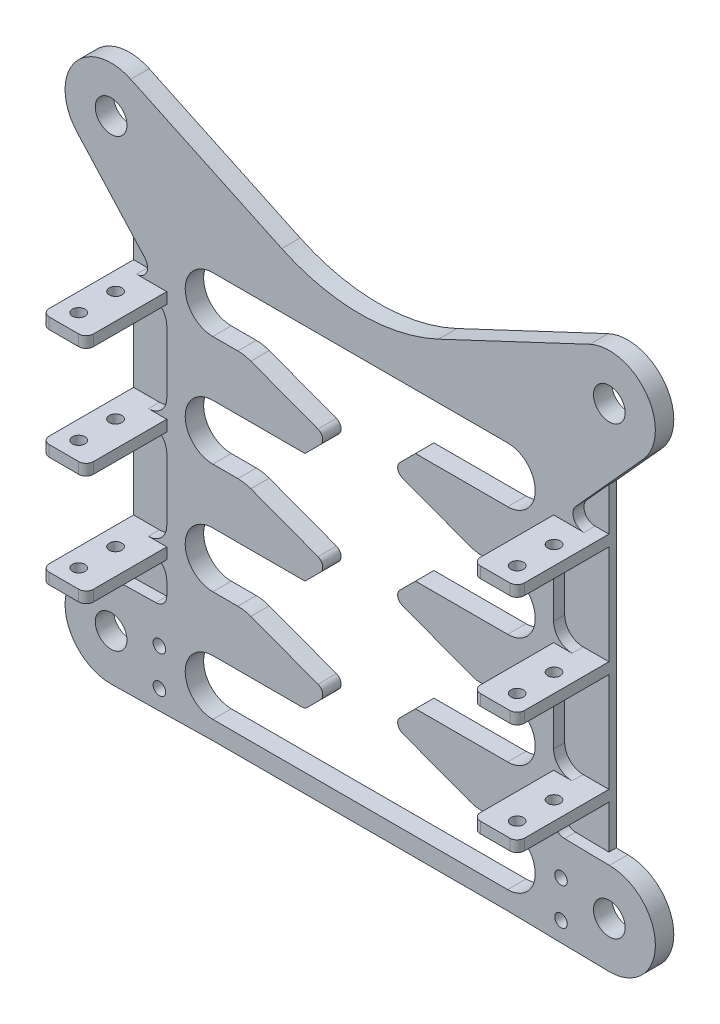
SolidWorks part; units mm, degrees
ref_plane "Front Plane" through (0, 0, 0) normal (0, 0, 1) x (1, 0, 0)
ref_plane "Top Plane" through (0, 0, 0) normal (0, 1, 0) x (1, 0, 0)
ref_plane "Right Plane" through (0, 0, 0) normal (1, 0, 0) x (0, 0, -1)
ref_plane "Plane1" through (0, 0, 60) normal (0, 0, 1) x (1, 0, 0)
sketch "Sketch2" plane through (0, 0, 60) normal (0, 0, 1) x (1, 0, 0)
  line L0 (0, 52) -> (-40, 52)
  line L1 (0, 52) -> (40, 52)
  line L2 (0, 52) -> (0, 82)
  line L3 (0, 52) -> (0, 22)
  line L4 (0, 82) -> (40, 82)
  line L5 (0, 82) -> (-40, 82)
  line L6 (0, 22) -> (40, 22)
  line L7 (0, 22) -> (-40, 22)
  line L8 (0, 22) -> (0, -8)
  line L9 (0, -8) -> (40, -8)
  line L10 (0, -8) -> (-40, -8)
  line L11 (40, 82) -> (-40, 82) construction
  line L12 (40, 74.5) -> (-40, 74.5)
  line L13 (40, 89.5) -> (-40, 89.5)
  line L14 (-40, 52) -> (40, 52) construction
  line L15 (-40, 59.5) -> (40, 59.5)
  line L16 (-40, 44.5) -> (40, 44.5)
  line L17 (40, 22) -> (-40, 22) construction
  line L18 (40, 14.5) -> (-40, 14.5)
  line L19 (40, 29.5) -> (-40, 29.5)
  line L20 (40, -8) -> (-40, -8) construction
  line L21 (40, -15.5) -> (-40, -15.5)
  line L22 (40, -0.5) -> (-40, -0.5)
  line L23 (0, -8) -> (0, 82) construction
  line L24 (-7.5, -8) -> (-7.5, 82)
  line L25 (7.5, -8) -> (7.5, 82)
  line L26 (40, 69.5) -> (-40, 69.5)
  line L27 (40, 94.5) -> (-40, 94.5)
  line L28 (-40, 64.5) -> (40, 64.5)
  line L29 (-40, 39.5) -> (40, 39.5)
  line L30 (-12.5, -8) -> (-12.5, 82)
  line L31 (12.5, -8) -> (12.5, 82)
  line L32 (40, 9.5) -> (-40, 9.5)
  line L33 (40, 34.5) -> (-40, 34.5)
  line L34 (40, -20.5) -> (-40, -20.5)
  line L35 (40, 4.5) -> (-40, 4.5)
  arc A0 (40, 74.5) -> (40, 89.5) centre (40, 82) ccw
  arc A1 (-40, 89.5) -> (-40, 74.5) centre (-40, 82) ccw
  arc A2 (-40, 59.5) -> (-40, 44.5) centre (-40, 52) ccw
  arc A3 (40, 44.5) -> (40, 59.5) centre (40, 52) ccw
  arc A4 (40, 14.5) -> (40, 29.5) centre (40, 22) ccw
  arc A5 (-40, 29.5) -> (-40, 14.5) centre (-40, 22) ccw
  arc A6 (40, -15.5) -> (40, -0.5) centre (40, -8) ccw
  arc A7 (-40, -0.5) -> (-40, -15.5) centre (-40, -8) ccw
  arc A8 (-7.5, -8) -> (7.5, -8) centre (0, -8) ccw
  arc A9 (7.5, 82) -> (-7.5, 82) centre (0, 82) ccw
  arc A10 (-40, 94.5) -> (-40, 69.5) centre (-40, 82) ccw
  arc A11 (40, 69.5) -> (40, 94.5) centre (40, 82) ccw
  arc A12 (40, 39.5) -> (40, 64.5) centre (40, 52) ccw
  arc A13 (-40, 64.5) -> (-40, 39.5) centre (-40, 52) ccw
  arc A14 (12.5, 82) -> (-12.5, 82) centre (0, 82) ccw
  arc A15 (-12.5, -8) -> (12.5, -8) centre (0, -8) ccw
  arc A16 (-40, 34.5) -> (-40, 9.5) centre (-40, 22) ccw
  arc A17 (40, 9.5) -> (40, 34.5) centre (40, 22) ccw
  arc A18 (-40, 4.5) -> (-40, -20.5) centre (-40, -8) ccw
  arc A19 (40, -20.5) -> (40, 4.5) centre (40, -8) ccw
  point P3 (0, 82)
  point P19 (0, 52)
  point P24 (0, 22)
  point P29 (0, -8)
  point P34 (0, 37)
  dimension "D1" = 40
  dimension "D2" = 40
  dimension "D3" = 30
  dimension "D4" = 30
  dimension "D5" = 30
  dimension "D6" = 40
  dimension "D7" = 40
  dimension "D8" = 40
  dimension "D9" = 40
  dimension "D10" = 40
  dimension "D11" = 40
  dimension "D12" = 15
  dimension "D13" = 15
  dimension "D14" = 15
  dimension "D15" = 15
  dimension "D16" = 15
  dimension "D17" = 5
extrude "Boss-Extrude2" add sketch "Sketch2" along normal blind 5 contours A14 L13 A0 L12 L31 L26 A11 L27 | L29 A12 L28 L31 L15 A3 L16 | L32 A17 L33 L31 L19 A4 L18 | L34 A19 L35 L31 L22 A6 L21 A15 | L31 L35 L25 L22 | L35 L31 L32 L25 | L32 L31 L18 L25 | L31 L33 L25 L19 | L33 L31 L29 L25 | L29 L31 L16 L25 | L15 L31 L28 L25 | L28 L31 L26 L25 | L26 L31 L12 L25 | L13 A14 | L21 A15 | L35 A18 L34 A15 L21 A7 L22 L30 | L24 L35 L30 L22 | L35 L24 L32 L30 | L32 L24 L18 L30 | L33 A16 L32 L30 L18 A5 L19 | L24 L33 L30 L19 | L33 L24 L29 L30 | L30 L29 L24 L16 | L28 A13 L29 L30 L16 A2 L15 | L30 L15 L24 L28 | L30 L28 L24 L26 | L30 L26 L24 L12 | A14 L27 A10 L26 L30 L12 A1 L13 region at (-10, 42, 60) region at (-10, 62, 60) region at (10, 42, 60) region at (10, 62, 60) region at (-12.9717, 42, 60) region at (-10, 37, 60) region at (-10, 67, 60) region at (26.25, 44.0283, 60) region at (10, 37, 60) region at (10, 67, 60) region at (-10, 32, 60) region at (-10, 72, 60) region at (10, 32, 60) region at (10, 72, 60) region at (-12.9717, 32, 60) region at (-26.25, 70.0815, 60) region at (26.25, 34.0283, 60) region at (13.0815, 72, 60) region at (-10, 12, 60) region at (0, 91.5388, 60) region at (10, 12, 60) region at (-10, 7, 60) region at (10, 7, 60) region at (-10, 2, 60) region at (-13.0815, 2, 60) region at (26.25, 3.9185, 60) region at (10, 2, 60) region at (0, -17.5388, 60)
chamfer "Chamfer1" distance 7.5 angle 45 12 edges at (7.5, 44.5, 62.5) (-7.5, 44.5, 62.5) (-7.5, 14.5, 62.5) (7.5, 14.5, 62.5) (-7.5, 29.5, 62.5) (-7.5, -0.5, 62.5) (7.5, -0.5, 62.5) (7.5, 29.5, 62.5) (-7.5, 74.5, 62.5) (-7.5, 59.5, 62.5) (7.5, 74.5, 62.5) (7.5, 59.5, 62.5)
chamfer "Chamfer2" distance 5 angle 45 12 edges at (12.5, 64.5, 62.5) (12.5, 69.5, 62.5) (12.5, 34.5, 62.5) (12.5, 39.5, 62.5) (-12.5, 64.5, 62.5) (-12.5, 69.5, 62.5) (-12.5, 39.5, 62.5) (-12.5, 34.5, 62.5) (-12.5, 4.5, 62.5) (-12.5, 9.5, 62.5) (12.5, 9.5, 62.5) (12.5, 4.5, 62.5)
fillet "Fillet2" radius 1.5 18 edges at (17.5, 64.5, 62.5) (17.5, 69.5, 62.5) (17.5, 39.5, 62.5) (17.5, 34.5, 62.5) (17.5, 9.5, 62.5) (17.5, 4.5, 62.5) (-17.5, 69.5, 62.5) (-17.5, 64.5, 62.5) (-17.5, 39.5, 62.5) (-17.5, 34.5, 62.5) (-17.5, 4.5, 62.5) (-17.5, 9.5, 62.5) (-15, 67, 62.5) (15, 67, 62.5) (-15, 37, 62.5) (15, 37, 62.5) (-15, 7, 62.5) (15, 7, 62.5)
sketch "Sketch3" plane through (0, 0, 60) normal (0, 0, -1) x (-1, 0, 0)
  line L0 (-67.6066, -21.0066) -> (-40, -20.5)
  line L1 (67.6066, -21.0066) -> (40, -20.5)
  line L2 (67.6066, 3.9934) -> (40, 4.5)
  line L3 (-67.6066, 3.9934) -> (-40, 4.5)
  line L4 (-62.2831, 123.8164) -> (0, 94.5)
  line L5 (-76.875, 104.1193) -> (-49.2684, 73.6127)
  line L6 (-40, 94.5) -> (40, 94.5) construction
  line L7 (0, 94.5) -> (62.2831, 123.8164)
  line L8 (76.875, 104.1193) -> (49.2684, 73.6127)
  line L9 (-40, 94.5) -> (40, 94.5)
  circle A0 centre (67.6066, 112.5066) radius 4.3
  circle A1 centre (-67.6066, 112.5066) radius 4.3
  circle A2 centre (-67.6066, -8.5066) radius 4.3
  circle A3 centre (67.6066, -8.5066) radius 4.3
  circle A4 centre (67.6066, -8.5066) radius 12.5
  circle A5 centre (67.6066, 112.5066) radius 12.5
  circle A6 centre (-67.6066, 112.5066) radius 12.5
  circle A7 centre (-67.6066, -8.5066) radius 12.5
  arc A8 (-40, 94.5) -> (-40, 69.5) centre (-40, 82) ccw construction
  arc A9 (-40, 94.5) -> (-49.2684, 73.6127) centre (-40, 82) ccw
  arc A10 (40, 69.5) -> (40, 94.5) centre (40, 82) ccw construction
  arc A11 (49.2684, 73.6127) -> (40, 94.5) centre (40, 82) ccw
  arc A12 (40, -20.5) -> (40, 4.5) centre (40, -8) ccw construction
  arc A13 (-40, 4.5) -> (-40, -20.5) centre (-40, -8) ccw construction
  arc A14 (40, -20.5) -> (40, 4.5) centre (40, -8) ccw
  arc A15 (-40, 4.5) -> (-40, -20.5) centre (-40, -8) ccw
extrude "Boss-Extrude3" add sketch "Sketch3" against normal blind 5 contours A9 L9 L4 A6 L5 | A6 A1 | A11 L8 A5 L7 L9 | A5 A0 | A4 L1 A3 | A14 L1 A4 L2 | A7 L0 A2 | A15 L3 A7 L0 region at (79.753, -8.5066, 60) region at (53.8033, -8.2533, 60) region at (-67.3838, -20.6489, 60) region at (-53.8033, -8.2533, 60) region at (-43.2431, 100.4549, 60) region at (43.2431, 100.4549, 60) region at (57.3507, 119.0144, 60) region at (-74.1144, 122.7625, 60)
fillet "Fillet3" radius 50 1 edges at (0, 94.5, 62.5)
sketch "Sketch4" plane through (0, 0, 65) normal (0, 0, 1) x (1, 0, 0)
  line L0 (-17.0607, 9.0607) -> (-16.0607, 8.0607) construction
  line L1 (-16.0607, 5.9393) -> (-17.0607, 4.9393) construction
  line L2 (-67.6066, 3.9934) -> (-40.4586, 4.4916) construction
  line L3 (-18.1213, 4.5) -> (-40, 4.5) construction
  line L4 (-18.1213, 9.5) -> (-40, 9.5) construction
  line L5 (-18.1213, 34.5) -> (-40, 34.5) construction
  line L6 (-16.0607, 35.9393) -> (-17.0607, 34.9393) construction
  line L7 (-17.0607, 39.0607) -> (-16.0607, 38.0607) construction
  line L8 (-40, 39.5) -> (-18.1213, 39.5) construction
  line L9 (-40, 64.5) -> (-18.1213, 64.5) construction
  line L10 (-16.0607, 65.9393) -> (-17.0607, 64.9393) construction
  line L11 (-17.0607, 69.0607) -> (-16.0607, 68.0607) construction
  line L12 (-18.1213, 69.5) -> (-40, 69.5) construction
  line L13 (-17.0607, 9.0607) -> (-16.0607, 8.0607)
  line L14 (-16.0607, 5.9393) -> (-17.0607, 4.9393)
  line L15 (-67.6066, 3.9934) -> (-40.4586, 4.4916)
  line L16 (-18.1213, 4.5) -> (-40, 4.5)
  line L17 (-18.1213, 9.5) -> (-40, 9.5)
  line L18 (-18.1213, 34.5) -> (-40, 34.5)
  line L19 (-16.0607, 35.9393) -> (-17.0607, 34.9393)
  line L20 (-17.0607, 39.0607) -> (-16.0607, 38.0607)
  line L21 (-40, 39.5) -> (-18.1213, 39.5)
  line L22 (-40, 64.5) -> (-18.1213, 64.5)
  line L23 (-16.0607, 65.9393) -> (-17.0607, 64.9393)
  line L24 (-17.0607, 69.0607) -> (-16.0607, 68.0607)
  line L25 (-18.1213, 69.5) -> (-40, 69.5)
  line L26 (-52.5, 22) -> (-52.5, 82)
  line L27 (-52.5, 82) -> (-52.5, 0)
  line L28 (-76.875, 104.1193) -> (-49.2684, 73.6127) construction
  line L29 (-76.875, 104.1193) -> (-49.2684, 73.6127)
  arc A0 (-17.0607, 9.0607) -> (-18.1213, 9.5) centre (-18.1213, 8) ccw construction
  arc A1 (-16.0607, 5.9393) -> (-16.0607, 8.0607) centre (-17.1213, 7) ccw construction
  arc A2 (-18.1213, 4.5) -> (-17.0607, 4.9393) centre (-18.1213, 6) ccw construction
  arc A3 (-40, 34.5) -> (-40, 9.5) centre (-40, 22) ccw construction
  arc A4 (-18.1213, 34.5) -> (-17.0607, 34.9393) centre (-18.1213, 36) ccw construction
  arc A5 (-16.0607, 35.9393) -> (-16.0607, 38.0607) centre (-17.1213, 37) ccw construction
  arc A6 (-17.0607, 39.0607) -> (-18.1213, 39.5) centre (-18.1213, 38) ccw construction
  arc A7 (-49.2684, 73.6127) -> (-40, 69.5) centre (-40, 82) ccw construction
  arc A8 (-40, 64.5) -> (-40, 39.5) centre (-40, 52) ccw construction
  arc A9 (-18.1213, 64.5) -> (-17.0607, 64.9393) centre (-18.1213, 66) ccw construction
  arc A10 (-16.0607, 65.9393) -> (-16.0607, 68.0607) centre (-17.1213, 67) ccw construction
  arc A11 (-17.0607, 69.0607) -> (-18.1213, 69.5) centre (-18.1213, 68) ccw construction
  arc A12 (-17.0607, 9.0607) -> (-18.1213, 9.5) centre (-18.1213, 8) ccw
  arc A13 (-16.0607, 5.9393) -> (-16.0607, 8.0607) centre (-17.1213, 7) ccw
  arc A14 (-18.1213, 4.5) -> (-17.0607, 4.9393) centre (-18.1213, 6) ccw
  arc A15 (-40, 34.5) -> (-40, 9.5) centre (-40, 22) ccw
  arc A16 (-18.1213, 34.5) -> (-17.0607, 34.9393) centre (-18.1213, 36) ccw
  arc A17 (-16.0607, 35.9393) -> (-16.0607, 38.0607) centre (-17.1213, 37) ccw
  arc A18 (-17.0607, 39.0607) -> (-18.1213, 39.5) centre (-18.1213, 38) ccw
  arc A19 (-49.2684, 73.6127) -> (-40, 69.5) centre (-40, 82) ccw
  arc A20 (-40, 64.5) -> (-40, 39.5) centre (-40, 52) ccw
  arc A21 (-18.1213, 64.5) -> (-17.0607, 64.9393) centre (-18.1213, 66) ccw
  arc A22 (-16.0607, 65.9393) -> (-16.0607, 68.0607) centre (-17.1213, 67) ccw
  arc A23 (-17.0607, 69.0607) -> (-18.1213, 69.5) centre (-18.1213, 68) ccw
  arc A24 (-40, 4.5) -> (-40.4586, 4.4916) centre (-40, -8) ccw construction
  arc A25 (-40, 4.5) -> (-40.4586, 4.4916) centre (-40, -8) ccw
extrude "Boss-Extrude4" add sketch "Sketch4" against normal up to surface (5 mm away) contours A25 L16 A14 L14 A13 L13 A12 L17 A15 L27 L15 | A20 L26 A15 L18 A16 L19 A17 L20 A18 L21 | L24 A23 L25 A19 L29 L27 A20 L22 A21 L23 A22 region at (-38.4155, 66.8833, 65) region at (-38.5639, 37, 65) region at (-36.8959, 7.8058, 65) up to face at (0, 39.4897, 60)
sketch "Sketch5" plane through (0, 0, 65) normal (0, 0, 1) x (1, 0, 0)
  line L0 (67.6066, 3.9934) -> (40.4586, 4.4916) construction
  line L1 (40, 4.5) -> (18.1213, 4.5) construction
  line L2 (17.0607, 4.9393) -> (16.0607, 5.9393) construction
  line L3 (16.0607, 8.0607) -> (17.0607, 9.0607) construction
  line L4 (40, 9.5) -> (18.1213, 9.5) construction
  line L5 (40, 34.5) -> (18.1213, 34.5) construction
  line L6 (17.0607, 34.9393) -> (16.0607, 35.9393) construction
  line L7 (16.0607, 38.0607) -> (17.0607, 39.0607) construction
  line L8 (18.1213, 39.5) -> (40, 39.5) construction
  line L9 (18.1213, 64.5) -> (40, 64.5) construction
  line L10 (17.0607, 64.9393) -> (16.0607, 65.9393) construction
  line L11 (16.0607, 68.0607) -> (17.0607, 69.0607) construction
  line L12 (40, 69.5) -> (18.1213, 69.5) construction
  line L13 (76.875, 104.1193) -> (49.2684, 73.6127) construction
  line L14 (67.6066, 3.9934) -> (40.4586, 4.4916)
  line L15 (40, 4.5) -> (18.1213, 4.5)
  line L16 (17.0607, 4.9393) -> (16.0607, 5.9393)
  line L17 (16.0607, 8.0607) -> (17.0607, 9.0607)
  line L18 (40, 9.5) -> (18.1213, 9.5)
  line L19 (40, 34.5) -> (18.1213, 34.5)
  line L20 (17.0607, 34.9393) -> (16.0607, 35.9393)
  line L21 (16.0607, 38.0607) -> (17.0607, 39.0607)
  line L22 (18.1213, 39.5) -> (40, 39.5)
  line L23 (18.1213, 64.5) -> (40, 64.5)
  line L24 (17.0607, 64.9393) -> (16.0607, 65.9393)
  line L25 (16.0607, 68.0607) -> (17.0607, 69.0607)
  line L26 (40, 69.5) -> (18.1213, 69.5)
  line L27 (52.5, 77.1838) -> (49.2684, 73.6127)
  line L28 (52.5, 22) -> (52.5, 4.2706)
  line L29 (52.5, 4.2706) -> (52.5, 77.1838)
  arc A0 (40.4586, 4.4916) -> (40, 4.5) centre (40, -8) ccw construction
  arc A1 (17.0607, 4.9393) -> (18.1213, 4.5) centre (18.1213, 6) ccw construction
  arc A2 (16.0607, 8.0607) -> (16.0607, 5.9393) centre (17.1213, 7) ccw construction
  arc A3 (18.1213, 9.5) -> (17.0607, 9.0607) centre (18.1213, 8) ccw construction
  arc A4 (40, 9.5) -> (40, 34.5) centre (40, 22) ccw construction
  arc A5 (17.0607, 34.9393) -> (18.1213, 34.5) centre (18.1213, 36) ccw construction
  arc A6 (16.0607, 38.0607) -> (16.0607, 35.9393) centre (17.1213, 37) ccw construction
  arc A7 (18.1213, 39.5) -> (17.0607, 39.0607) centre (18.1213, 38) ccw construction
  arc A8 (40, 39.5) -> (40, 64.5) centre (40, 52) ccw construction
  arc A9 (17.0607, 64.9393) -> (18.1213, 64.5) centre (18.1213, 66) ccw construction
  arc A10 (16.0607, 68.0607) -> (16.0607, 65.9393) centre (17.1213, 67) ccw construction
  arc A11 (18.1213, 69.5) -> (17.0607, 69.0607) centre (18.1213, 68) ccw construction
  arc A12 (40, 69.5) -> (49.2684, 73.6127) centre (40, 82) ccw construction
  arc A13 (40.4586, 4.4916) -> (40, 4.5) centre (40, -8) ccw
  arc A14 (17.0607, 4.9393) -> (18.1213, 4.5) centre (18.1213, 6) ccw
  arc A15 (16.0607, 8.0607) -> (16.0607, 5.9393) centre (17.1213, 7) ccw
  arc A16 (18.1213, 9.5) -> (17.0607, 9.0607) centre (18.1213, 8) ccw
  arc A17 (40, 9.5) -> (40, 34.5) centre (40, 22) ccw
  arc A18 (17.0607, 34.9393) -> (18.1213, 34.5) centre (18.1213, 36) ccw
  arc A19 (16.0607, 38.0607) -> (16.0607, 35.9393) centre (17.1213, 37) ccw
  arc A20 (18.1213, 39.5) -> (17.0607, 39.0607) centre (18.1213, 38) ccw
  arc A21 (40, 39.5) -> (40, 64.5) centre (40, 52) ccw
  arc A22 (17.0607, 64.9393) -> (18.1213, 64.5) centre (18.1213, 66) ccw
  arc A23 (16.0607, 68.0607) -> (16.0607, 65.9393) centre (17.1213, 67) ccw
  arc A24 (18.1213, 69.5) -> (17.0607, 69.0607) centre (18.1213, 68) ccw
  arc A25 (40, 69.5) -> (49.2684, 73.6127) centre (40, 82) ccw
extrude "Boss-Extrude5" add sketch "Sketch5" against normal up to surface (5 mm away) contours A25 L26 A24 L25 A23 L24 A22 L23 A21 L29 L27 | A21 L22 A20 L21 A19 L20 A18 L19 A17 L29 | A17 L18 A16 L17 A15 L16 A14 L15 A13 L14 L28 region at (38.4155, 66.8833, 65) region at (38.5639, 37, 65) region at (36.8959, 7.8058, 65) up to face at (13.901, 41.0917, 60)
sketch "Sketch7" plane through (0, 0, 65) normal (0, 0, 1) x (1, 0, 0)
  line L0 (-47.5, 52) -> (-48.5, 52)
  line L1 (-47.5, 22) -> (-48.5, 22)
  line L2 (-47.5, -8) -> (-48.5, -8)
  line L3 (47.5, -8) -> (48.5, -8)
  line L4 (47.5, 22) -> (48.5, 22)
  line L5 (47.5, 52) -> (48.5, 52)
  line L6 (47.5, 82) -> (48.5, 82)
  line L7 (-47.5, 82) -> (-48.5, 82)
  line L8 (-47.5, 53) -> (-48.5, 53)
  line L9 (-47.5, 23) -> (-48.5, 23)
  line L10 (-47.5, -7) -> (-48.5, -7)
  line L11 (47.5, -9) -> (48.5, -9)
  line L12 (47.5, 21) -> (48.5, 21)
  line L13 (47.5, 51) -> (48.5, 51)
  line L14 (47.5, 81) -> (48.5, 81)
  line L15 (-47.5, 83) -> (-48.5, 83)
  line L16 (-47.5, 51) -> (-48.5, 51)
  line L17 (-47.5, 21) -> (-48.5, 21)
  line L18 (-47.5, -9) -> (-48.5, -9)
  line L19 (47.5, -7) -> (48.5, -7)
  line L20 (47.5, 23) -> (48.5, 23)
  line L21 (47.5, 53) -> (48.5, 53)
  line L22 (47.5, 83) -> (48.5, 83)
  line L23 (-47.5, 81) -> (-48.5, 81)
  line L24 (-47.5, 53) -> (-47.5, 51)
  line L25 (-48.5, 51) -> (-48.5, 53)
  line L26 (-48.5, 83) -> (-48.5, 81)
  line L27 (-47.5, 81) -> (-47.5, 83)
  line L28 (48.5, 83) -> (48.5, 81)
  line L29 (47.5, 81) -> (47.5, 83)
  line L30 (47.5, 53) -> (47.5, 51)
  line L31 (48.5, 51) -> (48.5, 53)
  line L32 (47.5, 23) -> (47.5, 21)
  line L33 (48.5, 23) -> (48.5, 21)
  line L34 (47.5, -7) -> (47.5, -9)
  line L35 (48.5, -9) -> (48.5, -7)
  line L36 (-47.5, -7) -> (-47.5, -9)
  line L37 (-48.5, -7) -> (-48.5, -9)
  line L38 (-47.5, 21) -> (-47.5, 23)
  line L39 (-48.5, 23) -> (-48.5, 21)
  arc A0 (-40, 59.5) -> (-40, 44.5) centre (-40, 52) ccw construction
  arc A1 (-40, 29.5) -> (-40, 14.5) centre (-40, 22) ccw construction
  arc A2 (-40, -0.5) -> (-40, -15.5) centre (-40, -8) ccw construction
  arc A3 (40, -15.5) -> (40, -0.5) centre (40, -8) ccw construction
  arc A4 (40, 14.5) -> (40, 29.5) centre (40, 22) ccw construction
  arc A5 (40, 44.5) -> (40, 59.5) centre (40, 52) ccw construction
  arc A6 (40, 74.5) -> (40, 89.5) centre (40, 82) ccw construction
  arc A7 (-40, 89.5) -> (-40, 74.5) centre (-40, 82) ccw construction
  dimension "D1" = 1
  dimension "D2" = 1
  dimension "D3" = 1
extrude "Boss-Extrude6" add sketch "Sketch7" along normal blind 5 contours L29 L6 L28 L22 | L29 L14 L28 L6 | L5 L31 L21 L30 | L13 L31 L5 L30 | L33 L20 L32 L4 | L33 L4 L32 L12 | L3 L35 L19 L34 | L11 L35 L3 L34 | L10 L37 L2 L36 | L2 L37 L18 L36 | L9 L39 L1 L38 | L1 L39 L17 L38 | L25 L0 L24 L8 | L25 L16 L24 L0 | L7 L27 L15 L26 | L23 L27 L7 L26 region at (-48, 51.5, 65) region at (-48, 52.5, 65) region at (-48, 21.5, 65) region at (-48, 22.5, 65) region at (-48, -8.5, 65) region at (-48, -7.5, 65) region at (48, -7.5, 65) region at (48, -8.5, 65) region at (48, 22.5, 65) region at (48, 21.5, 65) region at (48, 52.5, 65) region at (48, 51.5, 65) region at (48, 82.5, 65) region at (48, 81.5, 65) region at (-48, 81.5, 65) region at (-48, 82.5, 65)
sketch "Sketch8" plane through (0, 0, 65) normal (0, 0, 1) x (1, 0, 0)
  circle A0 centre (-54.5, -5.5) radius 1.7
  circle A1 centre (-54.5, -15.5) radius 1.7
  dimension "D1" = 3.4
  dimension "D2" = 3.4
extrude "Cut-Extrude1" cut sketch "Sketch8" against normal blind 10
sketch "Sketch9" plane through (0, 0, 65) normal (0, 0, 1) x (1, 0, 0)
  circle A0 centre (54.5, -5.5) radius 1.7
  circle A1 centre (54.5, -15.5) radius 1.7
  dimension "D1" = 3.4
  dimension "D2" = 3.4
extrude "Cut-Extrude2" cut sketch "Sketch9" against normal blind 10
sketch "Sketch10" plane through (0, 0, 65) normal (0, 0, 1) x (1, 0, 0)
  line L0 (-40, 82) -> (40, 52)
  line L1 (-40, 52) -> (40, 22)
  line L2 (-40, 22) -> (40, -8)
  line L3 (-41.4045, 78.2547) -> (38.5955, 48.2547)
  line L4 (-38.5955, 85.7453) -> (41.4045, 55.7453)
  line L5 (-41.4045, 48.2547) -> (38.5955, 18.2547)
  line L6 (-38.5955, 55.7453) -> (41.4045, 25.7453)
  line L7 (-41.4045, 18.2547) -> (38.5955, -11.7453)
  line L8 (-38.5955, 25.7453) -> (41.4045, -4.2547)
  circle A0 centre (-40, 52) radius 4
  circle A1 centre (-40, 82) radius 4
  circle A2 centre (40, 52) radius 4
  circle A3 centre (40, 22) radius 4
  circle A4 centre (40, -8) radius 4
  circle A5 centre (-40, 22) radius 4
  dimension "D1" = 4
  dimension "D2" = 4
  dimension "D3" = 4
  dimension "D4" = 4
  dimension "D5" = 4
  dimension "D6" = 4
extrude "Cut-Extrude3" cut sketch "Sketch10" against normal blind 10 contours A2 L4 A1 L0 | A2 L0 A1 L3 | A1 | A2 | A3 L6 A0 L1 | A3 L1 A0 L5 | A0 | A3 | A5 L7 A4 L2 | A5 L2 A4 L8 | A5 region at (0.7107, 68.8951, 65) region at (-0.7107, 65.1049, 65) region at (-38.3916, 78.4615, 65) region at (38.3916, 55.5385, 65) region at (0.7107, 38.8951, 65) region at (-0.7107, 35.1049, 65) region at (-38.3916, 48.4615, 65) region at (38.3916, 25.5385, 65) region at (0.7107, 8.8951, 65) region at (-0.7107, 5.1049, 65) region at (-38.3916, 18.4615, 65)
fillet "Fillet4" radius 10 5 edges at (31.392, -0.5, 62.5) (31.392, 59.5, 62.5) (-31.392, 74.5, 62.5) (-31.392, 14.5, 62.5) (-31.392, 44.5, 62.5)
fillet "Fillet5" radius 2 7 edges at (8.5615, 38.0615, 62.5) (8.5615, 68.0615, 62.5) (-8.5615, 65.9385, 62.5) (-8.5615, 35.9385, 62.5) (8.5615, 8.0615, 62.5) (-15, -0.5, 62.5) (-8.5615, 5.9385, 62.5)
sketch "Sketch12" plane through (-52.5, 0, 0) normal (-1, 0, 0) x (0, 0, 1)
  line L0 (65, 48.8) -> (86.9, 48.8)
  line L1 (86.9, 48.8) -> (86.9, 45.8)
  line L2 (86.9, 45.8) -> (60, 45.8)
  line L3 (60, 4.2706) -> (60, 77.1838) construction
  line L4 (60, 45.8) -> (60, 48.8)
  line L5 (60, 48.8) -> (65, 48.8)
  line L6 (86.9, 18.8) -> (86.9, 15.8)
  line L7 (86.9, 15.8) -> (60, 15.8)
  line L8 (60, 15.8) -> (60, 18.8)
  line L9 (60, 18.8) -> (86.9, 18.8)
  line L10 (86.9, 78.8) -> (60, 78.8)
  line L11 (60, 104.1193) -> (60, 77.1838) construction
  line L12 (60, 78.8) -> (60, 75.8)
  line L13 (60, 75.8) -> (86.9, 75.8)
  line L14 (86.9, 75.8) -> (86.9, 78.8)
  dimension "D1" = 3
  dimension "D2" = 3
  dimension "D3" = 3
extrude "Boss-Extrude7" add sketch "Sketch12" along normal blind 12
sketch "Sketch13" plane through (-52.5, 0, 0) normal (-1, 0, 0) x (0, 0, 1)
  line L0 (86.9, 78.8) -> (60, 78.8) construction
  line L1 (60, 3.9934) -> (62, 3.9934)
  line L2 (60, 3.9934) -> (60, 78.8)
  line L3 (60, 78.8) -> (62, 78.8)
  line L4 (62, 3.9934) -> (62, 78.8)
  dimension "D1" = 2
extrude "Boss-Extrude8" add sketch "Sketch13" along normal blind 12
sketch "Sketch14" plane through (0, 78.8, 0) normal (0, 1, 0) x (1, 0, 0)
  line L1 (-64.5, -60) -> (-53.9626, -60)
  line L2 (-64.5, -60) -> (-64.5, -62)
  line L3 (-64.5, -62) -> (-53.9626, -62)
  line L4 (-53.9626, -60) -> (-53.9626, -62)
  dimension "D1" = 2
extrude "Boss-Extrude9" add sketch "Sketch14" along normal blind 20
fillet "Fillet6" radius 3 2 edges at (-53.9626, 78.8, 63.5) (-52.5, 4.2706, 63.5)
fillet "Fillet7" radius 5 5 edges at (-52.5, 18.8, 63.5) (-52.5, 48.8, 63.5) (-52.5, 75.8, 63.5) (-52.5, 45.8, 63.5) (-52.5, 15.8, 63.5)
sketch "Sketch15" plane through (0, 78.8, 0) normal (0, 1, 0) x (1, 0, 0)
  circle A0 centre (-59.5, -81.9) radius 1.7
  circle A1 centre (-59.5, -71.9) radius 1.7
  dimension "D1" = 3.4
  dimension "D2" = 3.4
extrude "Cut-Extrude4" cut sketch "Sketch15" against normal through all both and the other way through all
sketch "Sketch16" plane through (52.5, 0, 0) normal (1, 0, 0) x (0, 0, -1)
  line L0 (-86.9, 48.8) -> (-65, 48.8) construction
  line L1 (-86.9, 15.8) -> (-65, 15.8)
  line L2 (-86.9, 15.8) -> (-86.9, 18.8)
  line L3 (-86.9, 18.8) -> (-65, 18.8)
  line L4 (-65, 15.8) -> (-65, 18.8)
  line L5 (-86.9, 45.8) -> (-65, 45.8)
  line L6 (-86.9, 45.8) -> (-86.9, 48.8)
  line L7 (-86.9, 48.8) -> (-65, 48.8)
  line L8 (-65, 45.8) -> (-65, 48.8)
  line L9 (-65, 4.2706) -> (-65, 77.1838) construction
  line L10 (-65, 104.1193) -> (-65, 77.1838) construction
  line L11 (-86.9, 75.8) -> (-65, 75.8)
  line L12 (-86.9, 75.8) -> (-86.9, 78.8)
  line L13 (-86.9, 78.8) -> (-65, 78.8)
  line L14 (-65, 75.8) -> (-65, 78.8)
  line L15 (-86.9, 78.8) -> (-65, 78.8) construction
  line L16 (-60, 77.1838) -> (-60, 4.2706) construction
  line L17 (-65, 18.8) -> (-60, 18.8)
  line L18 (-65, 18.8) -> (-65, 15.8)
  line L19 (-65, 15.8) -> (-60, 15.8)
  line L20 (-60, 18.8) -> (-60, 15.8)
  line L21 (-60, 104.1193) -> (-62, 104.1193)
  line L22 (-65, 48.8) -> (-60, 48.8)
  line L23 (-65, 48.8) -> (-65, 45.8)
  line L24 (-65, 45.8) -> (-60, 45.8)
  line L25 (-60, 48.8) -> (-60, 45.8)
  line L26 (-65, 78.8) -> (-60, 78.8)
  line L27 (-65, 78.8) -> (-65, 75.8)
  line L28 (-65, 75.8) -> (-60, 75.8)
  line L29 (-60, 78.8) -> (-60, 75.8)
  line L30 (-62, 104.1193) -> (-62, 3.4363)
  line L31 (-62, 3.4363) -> (-60, 3.4363)
  line L32 (-60, -21.0066) -> (-60, 3.9934) construction
  line L33 (-60, 3.4363) -> (-60, 104.1193)
  line M5 (-60, 4.2706) -> (-60, 77.1838)
  line M6 (-60, 77.1838) -> (-65, 77.1838)
  line M7 (-65, 77.1838) -> (-65, 4.2706)
  line M8 (-65, 4.2706) -> (-60, 4.2706)
  dimension "D1" = 2
extrude "Boss-Extrude13" add sketch "Sketch16" along normal blind 12 contours L26 L33 L21 L30 | L28 L30 L22 M5 | L24 L30 L17 M5 | L19 L30 M8 M5 | L17 L30 L19 M5 | L30 L17 L19 M7 | L3 L2 L1 M7 | L7 L6 L5 M7 | L30 L22 L24 M7 | L22 L30 L24 M5 | L30 L28 M6 M5 | L30 L28 M6 M7 | L14 L13 L12 L11 M7 | L26 L30 L29 M6 | L30 L26 L14 M6 region at (52.5, 17.3, 75.95) region at (52.5, 17.3, 63.5) region at (52.5, 17.3, 61) region at (52.5, 10.0353, 61) region at (52.5, 32.3, 61) region at (52.5, 47.3, 75.95) region at (52.5, 47.3, 63.5) region at (52.5, 47.3, 61) region at (52.5, 62.3, 61) region at (52.5, 77.3, 75.95) region at (52.5, 76.4919, 63.5) region at (52.5, 76.4919, 61) region at (52.5, 77.9919, 63.5) region at (52.5, 77.9919, 61) region at (52.5, 91.4596, 61)
sketch "Sketch17" plane through (0, 4.2706, 0) normal (0, -1, 0) x (1, 0, 0)
  line L4 (52.5, 62) -> (52.5, 60)
  line L5 (52.5, 60) -> (64.5, 60)
  line L6 (64.5, 60) -> (64.5, 62)
  line L7 (64.5, 62) -> (52.5, 62)
  line L8 (52.5, 62) -> (52.5, 60)
  line L9 (52.5, 60) -> (64.5, 60)
  line L10 (64.5, 60) -> (64.5, 62)
  line L11 (64.5, 62) -> (52.5, 62)
  dimension "D1" = 0
extrude "Boss-Extrude14" add sketch "Sketch17" along normal blind 2
fillet "Fillet8" radius 5 5 edges at (52.5, 15.8, 63.5) (52.5, 45.8, 63.5) (52.5, 18.8, 63.5) (52.5, 48.8, 63.5) (52.5, 75.8, 63.5)
fillet "Fillet9" radius 3 2 edges at (52.5, 4.2706, 63.5) (53.9626, 78.8, 63.5)
sketch "Sketch19" plane through (0, 78.8, 0) normal (0, 1, 0) x (1, 0, 0)
  circle A0 centre (59.5, -81.9) radius 1.7
  circle A1 centre (59.5, -71.9) radius 1.7
  dimension "D1" = 3.4
  dimension "D2" = 3.4
extrude "Cut-Extrude5" cut sketch "Sketch19" against normal through all both and the other way through all
fillet "Fillet10" radius 2 12 edges at (-64.5, 17.3, 86.9) (-52.5, 17.3, 86.9) (-64.5, 47.3, 86.9) (-52.5, 47.3, 86.9) (-52.5, 77.3, 86.9) (-64.5, 77.3, 86.9) (64.5, 17.3, 86.9) (52.5, 17.3, 86.9) (64.5, 47.3, 86.9) (52.5, 47.3, 86.9) (52.5, 77.3, 86.9) (64.5, 77.3, 86.9)
sketch "Sketch20" plane through (0, 21, 0) normal (0, -1, 0) x (1, 0, 0)
  line L0 (67.6066, 65) -> (40, 65) construction
  line L1 (-48.5, 70) -> (-47.5, 70)
  line L2 (-48.5, 70) -> (-48.5, 65)
  line L3 (-48.5, 65) -> (-47.5, 65)
  line L4 (-47.5, 70) -> (-47.5, 65)
  line L5 (47.5, 70) -> (48.5, 70)
  line L6 (47.5, 70) -> (47.5, 65)
  line L7 (47.5, 65) -> (48.5, 65)
  line L8 (48.5, 70) -> (48.5, 65)
  line L9 (48.5, 70) -> (48.5, 65) construction
extrude "Cut-Extrude6" cut sketch "Sketch20" against normal through all both and the other way through all
